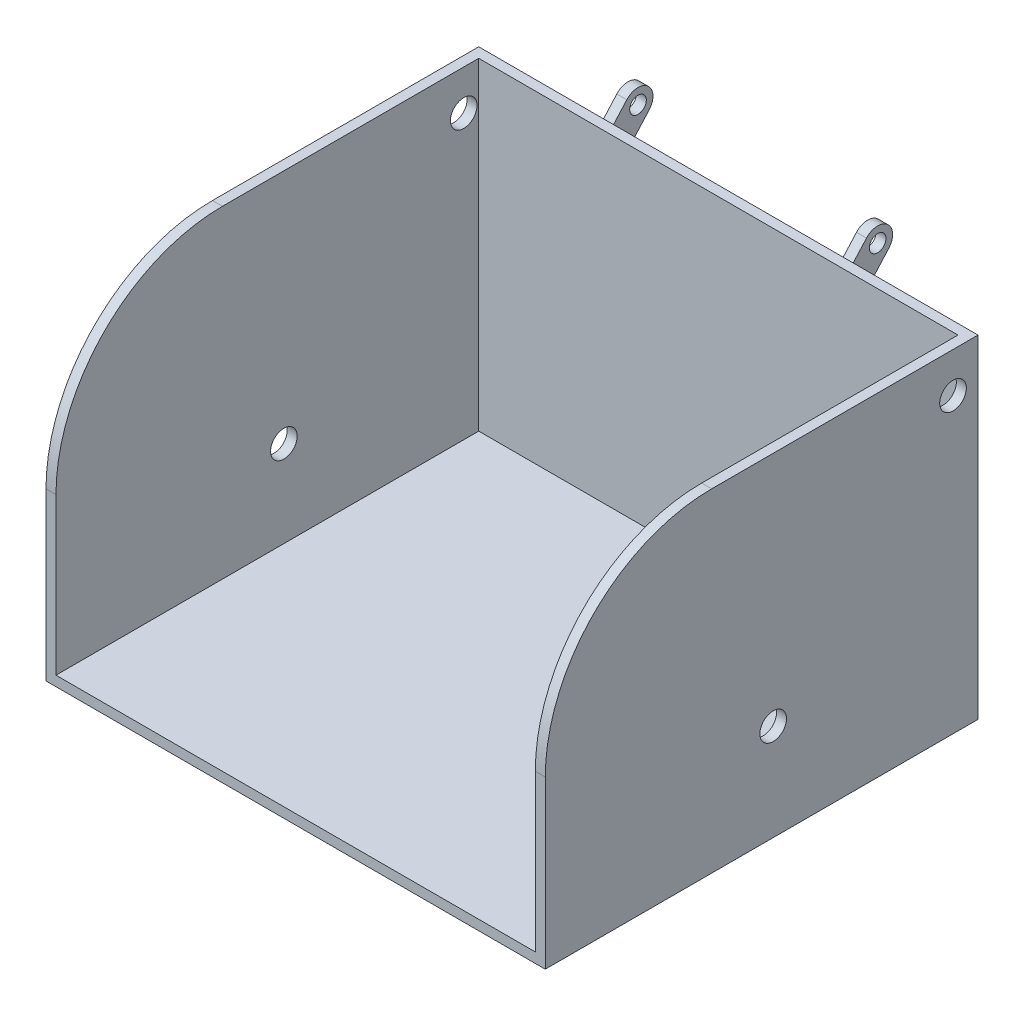
SolidWorks part; units mm, degrees
material "PLA"
ref_plane "Front Plane" through (0, 0, 0) normal (0, 0, 1) x (1, 0, 0)
ref_plane "Top Plane" through (0, 0, 0) normal (0, 1, 0) x (1, 0, 0)
ref_plane "Right Plane" through (0, 0, 0) normal (1, 0, 0) x (0, 0, -1)
sketch "Sketch1" plane through (0, 0, 0) normal (1, 0, 0) x (0, 0, -1)
  line L0 (0, 0) -> (-130, 0)
  line L1 (-130, 0) -> (-130, 50)
  line L2 (-80, 100) -> (0, 100)
  line L3 (0, 100) -> (0, 0)
  arc A0 (-130, 50) -> (-80, 100) centre (-80, 50) cw
  dimension "D1" = 130
  dimension "D2" = 100
  dimension "D3" = 50
extrude "Boss-Extrude1" add sketch "Sketch1" along normal blind 150 contours A0 L2 L3 L0 L1
sketch "Sketch2" plane through (0, 100, 0) normal (0, 1, 0) x (1, 0, 0)
  line L0 (150, 0) -> (0, 0) construction
  line L1 (3, -3) -> (147, -3)
  line L2 (3, -3) -> (3, -135)
  line L3 (3, -135) -> (147, -135)
  line L4 (147, -3) -> (147, -135)
  line L5 (150, -80) -> (150, 0) construction
  line L6 (0, -80) -> (0, 0) construction
  line L8 (150, -130) -> (0, -130) construction
  dimension "D1" = 3
  dimension "D2" = 3
  dimension "D3" = 3
  dimension "D4" = 5
extrude "Cut-Extrude1" cut sketch "Sketch2" against normal offset from surface (97 mm away) 3 up to face at (75, 0, 65)
ref_plane "Plane1" through (75, 0, 0) normal (1, 0, 0) x (0, 0, -1)
ref_plane "Plane2" through (111, 0, 0) normal (1, 0, 0) x (0, 0, -1)
ref_plane "Plane3" through (39, 0, 0) normal (1, 0, 0) x (0, 0, -1)
sketch "Sketch3" plane through (111, 0, 0) normal (1, 0, 0) x (0, 0, -1)
  line L0 (0, 100) -> (0, 86.4837)
  line L1 (0, 86.4837) -> (10.7098, 98.4837)
  line L2 (3.9952, 104.4764) -> (0, 100)
  arc A0 (10.7098, 98.4837) -> (3.9952, 104.4764) centre (7.3525, 101.4801) ccw
  circle A1 centre (7.3525, 101.4801) radius 2.5
  dimension "D1" = 2
  dimension "D2" = 5
  dimension "D3" = 6
  dimension "D4" = 12
extrude "Boss-Extrude2" add sketch "Sketch3" along normal mid plane 3
mirror "Mirror1" about plane through (75, 0, 0) normal (1, 0, 0) of "Boss-Extrude2"
sketch "Sketch4" plane through (150, 0, 0) normal (1, 0, 0) x (0, 0, -1)
  line L0 (-7.5037, 88) -> (-61.5315, 29) construction
  line L1 (0, 0) -> (-130, 0) construction
  line L2 (-80, 100) -> (0, 100) construction
  circle A0 centre (-61.5315, 29) radius 4
  circle A1 centre (-7.5037, 88) radius 4
  dimension "D4" = 8
  dimension "D5" = 8
  dimension "D1" = 80
  dimension "D2" = 29
  dimension "D3" = 12
extrude "Cut-Extrude2" cut sketch "Sketch4" against normal up to next contours A0 | A1 region at (150, 29, 61.5315) region at (150, 88, 7.5037)
mirror "Mirror2" about plane through (75, 0, 0) normal (1, 0, 0) of "Cut-Extrude2"
equation "\"forward_length\"= 130"
equation "\"height\"= 100"
equation "\"eslabon_AB\"=80"
